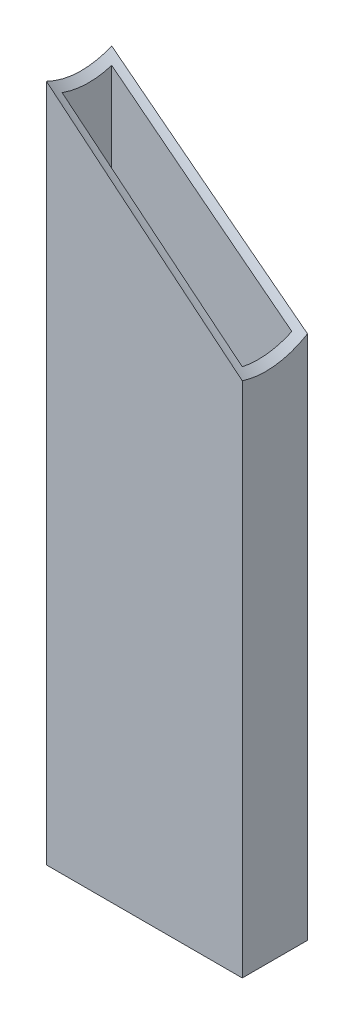
SolidWorks part; units mm, degrees
note: '?' marks a value the reader was unsure of.
material "A500"
ref_plane "Front Plane" through (0, 0, 0) normal (0, 0, 1) x (1, 0, 0)
ref_plane "Top Plane" through (0, 0, 0) normal (0, 1, 0) x (1, 0, 0)
ref_plane "Right Plane" through (0, 0, 0) normal (1, 0, 0) x (0, 0, -1)
sketch "Sketch1" plane through (0, 0, 0) normal (0, 1, 0) x (1, 0, 0)
  line L0 (0, 9.652) -> (0, 12.7) construction
  line L1 (-38.1, 12.7) -> (38.1, 12.7)
  line L2 (-38.1, 12.7) -> (-38.1, -12.7)
  line L3 (-38.1, -12.7) -> (38.1, -12.7)
  line L4 (38.1, 12.7) -> (38.1, -12.7)
  line L5 (-35.052, 9.652) -> (35.052, 9.652)
  line L6 (-35.052, 9.652) -> (-35.052, -9.652)
  line L7 (-35.052, -9.652) -> (35.052, -9.652)
  line L8 (35.052, 9.652) -> (35.052, -9.652)
  line L9 (35.052, 0) -> (38.1, 0) construction
  line L10 (0, -9.652) -> (0, -12.7) construction
  line L11 (-35.052, 0) -> (-38.1, 0) construction
  line L12 (0, 9.652) -> (0, 0) construction
  line L13 (0, 0) -> (-35.052, 0) construction
  dimension "D1" = 76.2
  dimension "D2" = 25.4
  dimension "D3" = 3.048
extrude "Boss-Extrude1" add sketch "Sketch1" along normal up to vertex (241.0919 mm away)
ref_plane "Plane1" through (0, 0, 0) normal (0, 0, 1) x (1, 0, 0)
sketch "Sketch2" plane through (0, 0, 0) normal (0, 0, 1) x (1, 0, 0)
  line L0 (0, 0) -> (0, 241.0919) construction
  line L1 (-38.1, 241.0919) -> (38.1, 241.0919) construction
  line L2 (0, 120.546) -> (-38.1, 120.546) construction
  line L3 (-38.1, 241.0919) -> (-38.1, 0) construction
  line L4 (0, 120.546) -> (38.1, 120.546) construction
  line L5 (38.1, 241.0919) -> (38.1, 0) construction
ref_axis "Axis1" through (0, 241.0919, 0) along (0, -1, 0)?
sketch "Sketch3" plane through (0, 241.0919, 0) normal (0, 1, 0) x (1, 0, 0)
  line L0 (35.052, -9.652) -> (35.052, 9.652) construction
  line L1 (35.052, 9.652) -> (-35.052, 9.652) construction
  line L2 (-35.052, -9.652) -> (35.052, -9.652) construction
  line L3 (-35.052, 9.652) -> (-35.052, -9.652) construction
  line L4 (-38.1, 12.7) -> (-38.1, -12.7)
  line L5 (-38.1, -12.7) -> (38.1, -12.7)
  line L6 (38.1, -12.7) -> (38.1, 12.7)
  line L7 (38.1, 12.7) -> (-38.1, 12.7)
  line L8 (-38.1, 12.7) -> (-38.1, -12.7)
  line L9 (-38.1, -12.7) -> (38.1, -12.7)
  line L10 (38.1, -12.7) -> (38.1, 12.7)
  line L11 (38.1, 12.7) -> (-38.1, 12.7)
  line L12 (35.052, -9.652) -> (35.052, 9.652)
  line L13 (35.052, 9.652) -> (-35.052, 9.652)
  line L14 (-35.052, -9.652) -> (35.052, -9.652)
  line L15 (-35.052, 9.652) -> (-35.052, -9.652)
  dimension "D1" = 0
extrude "Boss-Extrude2" add sketch "Sketch3" along normal blind 3.048
sketch "Sketch4" plane through (0, 0, 0) normal (0, -1, 0) x (1, 0, 0)
  line L0 (35.052, 9.652) -> (35.052, -9.652) construction
  line L1 (35.052, -9.652) -> (-35.052, -9.652) construction
  line L2 (-35.052, 9.652) -> (35.052, 9.652) construction
  line L3 (-35.052, -9.652) -> (-35.052, 9.652) construction
  line L4 (-38.1, 12.7) -> (-38.1, -12.7)
  line L5 (-38.1, -12.7) -> (38.1, -12.7)
  line L6 (38.1, -12.7) -> (38.1, 12.7)
  line L7 (38.1, 12.7) -> (-38.1, 12.7)
  line L8 (-38.1, 12.7) -> (-38.1, -12.7)
  line L9 (-38.1, -12.7) -> (38.1, -12.7)
  line L10 (38.1, -12.7) -> (38.1, 12.7)
  line L11 (38.1, 12.7) -> (-38.1, 12.7)
  line L12 (35.052, 9.652) -> (35.052, -9.652)
  line L13 (35.052, -9.652) -> (-35.052, -9.652)
  line L14 (-35.052, 9.652) -> (35.052, 9.652)
  line L15 (-35.052, -9.652) -> (-35.052, 9.652)
  dimension "D1" = 0
extrude "Boss-Extrude3" add sketch "Sketch4" along normal blind 38.1
ref_plane "Plane2" through (-107.3865, 327.1509, -6.1454) normal (0.7796, -0.6247, 0.0446) x (0.031, -0.0327, -0.999)
sketch "Sketch5" plane through (-107.3865, 327.1509, -6.1454) normal (0.7796, -0.6247, 0.0446) x (0.031, -0.0327, -0.999)
  circle A0 centre (0, 0) radius 38.1 construction
  circle A1 centre (0, 0) radius 38.1
extrude "Cut-Extrude2" cut sketch "Sketch5" along normal up to vertex
equation "\"tubeMainWidth\"= 76.2mm"
equation "\"tubeSecondWidth\"= 25.4mm"
equation "\"tubeThickness\"= 3.048mm"
equation "\"halfMainWidthOfTubing\"= (\"tubeMainWidth\"/2)"
equation "\"D1@Sketch1\"=\"tubeMainWidth\""
equation "\"D2@Sketch1\"=\"tubeSecondWidth\""
equation "\"D3@Sketch1\"=\"tubeThickness\""
equation "\"D1@Boss-Extrude2\"=\"tubeThickness\""
equation "\"D1@Boss-Extrude3\"=\"halfMainWidthOfTubing\""
